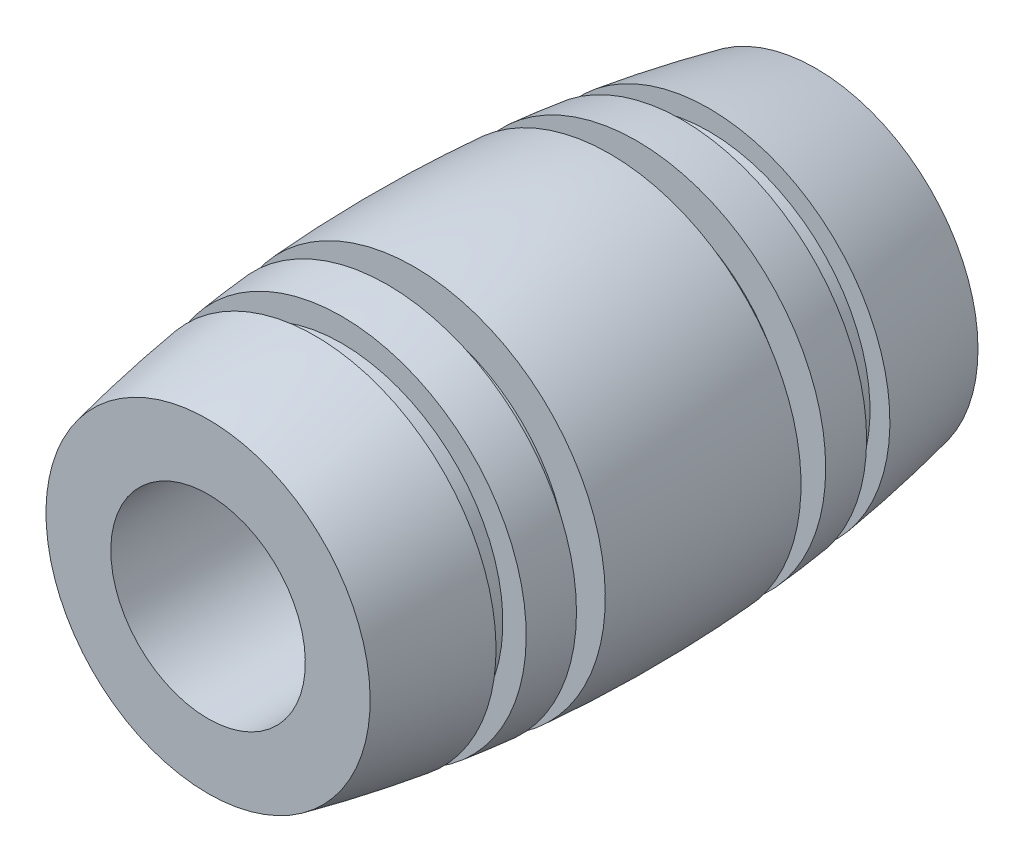
SolidWorks part; units mm, degrees
ref_plane "Front Plane" through (0, 0, 0) normal (0, 0, 1) x (1, 0, 0)
ref_plane "Top Plane" through (0, 0, 0) normal (0, 1, 0) x (1, 0, 0)
ref_plane "Right Plane" through (0, 0, 0) normal (1, 0, 0) x (0, 0, -1)
sketch "Sketch1" plane through (0, 0, 0) normal (0, 0, 1) x (1, 0, 0)
  line L0 (-8, 0) -> (8, 0) construction
  line L1 (-4, 0) -> (4, 0) construction
  circle A0 centre (0, 0) radius 8 construction
  circle A1 centre (0, 0) radius 4 construction
  point P2 (0, 0)
  point P6 (0, 0)
  point P10 (0, 8)
  point P11 (0, 4)
  point P12 (0, -4)
  point P13 (0, -8)
  dimension "OD" = 16
  dimension "ID" = 8
sketch "Sketch2" plane through (0, 0, 0) normal (1, 0, 0) x (0, 0, -1)
  line L0 (-12.5, 8) -> (12.5, 8) construction
  line L1 (-7, -8) -> (7, -8) construction
  line L2 (0, 0) -> (12.5, 0.2182) construction
  line L3 (12.5, 0.2182) -> (12.5, -0.2182) construction
  line L4 (12.5, -0.2182) -> (0, 0) construction
  point P2 (0, 8)
  point P6 (0, -8)
  point P7 (-8.1, -8)
  point P9 (5.125, -8)
  point P10 (8.1, -8)
  point P11 (-5.125, -8)
  point P17 (12.5, 0)
  dimension "L" = 25
  dimension "RR" = 14
  dimension "RRW" = 1.1
  dimension "D1" = 1.1
  dimension "D2" = 1.875
  dimension "D3" = 1.875
  dimension "D4" = 2
sketch "Sketch5" plane through (0, 0, 0) normal (1, 0, 0) x (0, 0, -1)
  line L0 (-12.5, 8) -> (-12.5, 6.6667) construction
  line L1 (-12.5, 6.6667) -> (-12.5, 5.3333) construction
  line L2 (-12.5, 5.3333) -> (-12.5, 4) construction
  line L3 (12.5, 8) -> (12.5, 6.6667) construction
  line L4 (12.5, 6.6667) -> (12.5, 5.3333) construction
  line L5 (12.5, 5.3333) -> (12.5, 4) construction
  line L9 (-12.5, 0) -> (12.5, 0) construction
  line L10 (-12.5, 8) -> (12.5, 8) construction
  line L12 (-12.5, 4) -> (12.5, 4)
  line L13 (12.5, 4) -> (12.5, 6.6667)
  line L15 (-12.5, 6.6667) -> (-12.5, 4)
  arc A1 (-12.5, 6.6667) -> (12.5, 6.6667) centre (0, -51.2604) cw
  point P12 (0, 8)
  point P18 (0, 0)
revolve "Revolve1" add sketch "Sketch5" angle 360 about L9
sketch "Sketch4" plane through (0, 0, 0) normal (1, 0, 0) x (0, 0, -1)
  line L0 (-12.5, 0) -> (12.5, 0) construction
  line L1 (-8.1, -8) -> (-7, -8)
  line L2 (-8.1, -8) -> (-8.1, -6.625)
  line L3 (-8.1, -6.625) -> (-7, -6.625)
  line L4 (-7, -8) -> (-7, -6.625)
  line L5 (-8.1, -8) -> (-7, -6.625) construction
  line L6 (-8.1, -6.625) -> (-7, -8) construction
  line L7 (7, -8) -> (8.1, -8)
  line L8 (7, -8) -> (7, -6.625)
  line L9 (7, -6.625) -> (8.1, -6.625)
  line L10 (8.1, -8) -> (8.1, -6.625)
  line L11 (7, -8) -> (8.1, -6.625) construction
  line L12 (7, -6.625) -> (8.1, -8) construction
  line L14 (-5.125, -8) -> (-4.025, -8)
  line L15 (-5.125, -8) -> (-5.125, -6.35)
  line L16 (-5.125, -6.35) -> (-4.025, -6.35)
  line L17 (-4.025, -8) -> (-4.025, -6.35)
  line L18 (-5.125, -8) -> (-4.025, -6.35) construction
  line L19 (-5.125, -6.35) -> (-4.025, -8) construction
  line L20 (5.125, -8) -> (4.025, -8)
  line L21 (5.125, -8) -> (5.125, -6.35)
  line L22 (5.125, -6.35) -> (4.025, -6.35)
  line L23 (4.025, -8) -> (4.025, -6.35)
  line L24 (5.125, -8) -> (4.025, -6.35) construction
  line L25 (5.125, -6.35) -> (4.025, -8) construction
  point P4 (-7.55, -7.3125)
  point P10 (7.55, -7.3125)
  point P12 (0, 0)
  point P25 (-4.575, -7.175)
  point P30 (4.575, -7.175)
  dimension "D1" = 1.65
  dimension "D2" = 1.375
revolve "Cut-Revolve1" cut sketch "Sketch4" angle 360 about L0
ref_plane "Contact Plane 1" through (0, 0, 12.5) normal (0, 0, 1) x (1, 0, 0)
ref_plane "Contact Plane 2" through (0, 0, -8.1) normal (0, 0, 1) x (1, 0, 0)
ref_axis "Center Axis 1" through (0, 0, -12.5) along (0, 0, 1)
equation "\"D1@Sketch2\"=\"RRW@Sketch2\""
equation "\"D2@Sketch2\"=\"L@Sketch2\"*.075"
equation "\"D3@Sketch2\"=\"L@Sketch2\"*.075"
equation "\"D1@Sketch4\"=\"RRW@Sketch2\"*1.5"
equation "\"D2@Sketch4\"=\"RRW@Sketch2\"*1.25"
